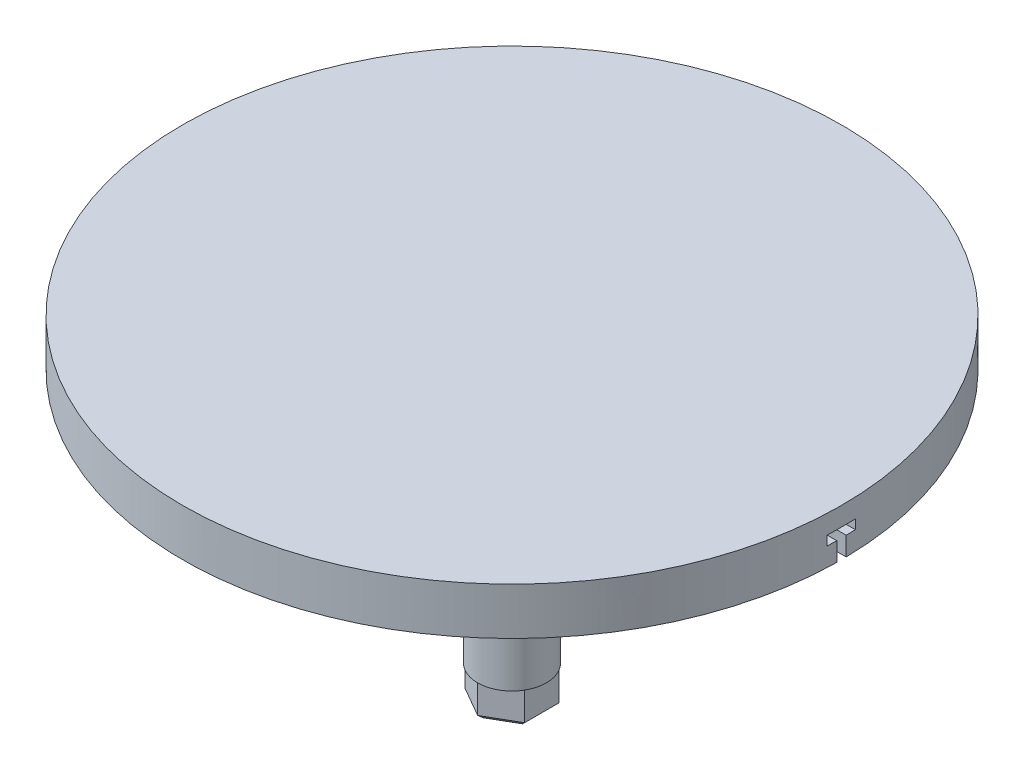
SolidWorks part; units mm, degrees
ref_plane "Front Plane" through (0, 0, 0) normal (0, 0, 1) x (1, 0, 0)
ref_plane "Top Plane" through (0, 0, 0) normal (0, 1, 0) x (1, 0, 0)
ref_plane "Right Plane" through (0, 0, 0) normal (1, 0, 0) x (0, 0, -1)
ref_plane "Plane6" through (0, 3, 0) normal (0, 1, 0) x (1, 0, 0)
sketch "Sketch3" plane through (0, 3, 0) normal (0, 1, 0) x (1, 0, 0)
  circle A0 centre (0, 0) radius 3.65
extrude "Boss-Extrude2" add sketch "Sketch3" along normal blind 27
sketch "Sketch4" plane through (0, 30, 0) normal (0, 1, 0) x (1, 0, 0)
  circle A0 centre (0, 0) radius 35
extrude "Boss-Extrude3" add sketch "Sketch4" along normal blind 5
ref_plane "Plane1" through (35, 0, 0) normal (1, 0, 0) x (0, 0, -1)
sketch "Sketch5" plane through (35, 0, 0) normal (1, 0, 0) x (0, 0, -1)
  line L1 (-0.5, 30) -> (0.5, 30)
  line L2 (0.5, 30) -> (0.5, 32)
  line L3 (-0.5, 32) -> (-1.5, 32)
  line L4 (-1.5, 32) -> (-1.5, 33)
  line L5 (-1.5, 33) -> (1.5, 33)
  line L6 (1.5, 33) -> (1.5, 32)
  line L7 (1.5, 32) -> (0.5, 32)
  line L8 (-0.5, 32) -> (-0.5, 30)
  line L9 (-3.65, 30) -> (3.65, 30) construction
  line L10 (-3.65, 30) -> (3.65, 30) construction
  line L11 (0, 30) -> (0, 28.5625) construction
  dimension "D1" = 2
  dimension "D2" = 2
  dimension "D3" = 1
  dimension "D4" = 3
extrude "Cut-Extrude2" cut sketch "Sketch5" against normal blind 31
ref_plane "Plane2" through (-35, 0, 0) normal (-1, 0, 0) x (0, 0, 1)
sketch "Sketch6" plane through (-35, 0, 0) normal (-1, 0, 0) x (0, 0, 1)
  line L0 (-0.5, 30) -> (-0.5, 32) construction
  line L1 (-0.5, 32) -> (-1.5, 32) construction
  line L2 (-1.5, 33) -> (-1.5, 32) construction
  line L3 (-1.5, 33) -> (1.5, 33) construction
  line L4 (1.5, 32) -> (1.5, 33) construction
  line L5 (1.5, 32) -> (0.5, 32) construction
  line L6 (0.5, 30) -> (0.5, 32) construction
  line L7 (-0.5, 30) -> (-0.5, 32)
  line L8 (-0.5, 32) -> (-1.5, 32)
  line L9 (-1.5, 33) -> (-1.5, 32)
  line L10 (-1.5, 33) -> (1.5, 33)
  line L11 (1.5, 32) -> (1.5, 33)
  line L12 (1.5, 32) -> (0.5, 32)
  line L13 (0.5, 30) -> (0.5, 32)
  line L14 (-0.5, 30) -> (0.5, 30)
  line L16 (-3.65, 30) -> (3.65, 30) construction
  point P10 (0, 30)
  dimension "D1" = 3.65
extrude "Cut-Extrude4" cut sketch "Sketch6" against normal blind 31
ref_plane "Plane3" through (0, 0, -35) normal (0, 0, -1) x (-1, 0, 0)
sketch "Sketch8" plane through (0, 0, -35) normal (0, 0, -1) x (-1, 0, 0)
  line L0 (-0.5, 30) -> (0.5, 30)
  line L1 (0.5, 30) -> (0.5, 32)
  line L2 (-0.5, 32) -> (-1.5, 32)
  line L3 (-1.5, 32) -> (-1.5, 33)
  line L4 (-1.5, 33) -> (1.5, 33)
  line L5 (1.5, 33) -> (1.5, 32)
  line L6 (1.5, 32) -> (0.5, 32)
  line L7 (-0.5, 32) -> (-0.5, 30)
  line L8 (-3.65, 30) -> (-0.5, 30) construction
  dimension "D1" = 2
  dimension "D2" = 2
  dimension "D3" = 1
  dimension "D4" = 3
  dimension "D5" = 3.15
  dimension "D6" = 1
extrude "Cut-Extrude5" cut sketch "Sketch8" against normal blind 31
ref_plane "Plane4" through (24.7487, 0, -24.7487) normal (0.7071, 0, -0.7071) x (0, -1, 0)
sketch "Sketch9" plane through (24.7487, 0, -24.7487) normal (0.7071, 0, -0.7071) x (0, -1, 0)
  line L0 (-30, -0.5) -> (-30, 0.5)
  line L1 (-30, 0.5) -> (-32, 0.5)
  line L2 (-32, -0.5) -> (-32, -1.5)
  line L3 (-32, -1.5) -> (-33, -1.5)
  line L4 (-33, -1.5) -> (-33, 1.5)
  line L5 (-33, 1.5) -> (-32, 1.5)
  line L6 (-32, 1.5) -> (-32, 0.5)
  line L7 (-32, -0.5) -> (-30, -0.5)
  line L8 (-30, -3.65) -> (-30, 3.65) construction
  line L9 (-30, 0) -> (-27.9245, 0) construction
  line L10 (-30, -3.65) -> (-30, 3.65) construction
  dimension "D1" = 2
  dimension "D2" = 2
  dimension "D3" = 1
  dimension "D4" = 3
extrude "Cut-Extrude6" cut sketch "Sketch9" against normal blind 31
ref_plane "Plane5" through (-24.7487, 0, -24.7487) normal (-0.7071, 0, -0.7071) x (0, -1, 0)
sketch "Sketch10" plane through (-24.7487, 0, -24.7487) normal (-0.7071, 0, -0.7071) x (0, -1, 0)
  line L0 (-30, -0.5) -> (-30, 0.5)
  line L1 (-30, 0.5) -> (-32, 0.5)
  line L2 (-32, -0.5) -> (-32, -1.5)
  line L3 (-32, -1.5) -> (-33, -1.5)
  line L4 (-33, -1.5) -> (-33, 1.5)
  line L5 (-33, 1.5) -> (-32, 1.5)
  line L6 (-32, 1.5) -> (-32, 0.5)
  line L7 (-32, -0.5) -> (-30, -0.5)
  line L8 (-30, -3.65) -> (-30, -0.5) construction
  dimension "D1" = 2
  dimension "D2" = 2
  dimension "D3" = 1
  dimension "D4" = 3
  dimension "D5" = 3.15
extrude "Cut-Extrude7" cut sketch "Sketch10" against normal blind 31
sketch "Sketch11" plane through (0, 3, 0) normal (0, -1, 0) x (1, 0, 0)
  line L1 (0, 3.65) -> (-3.161, 1.825)
  line L2 (-3.161, 1.825) -> (-3.161, -1.825)
  line L3 (-3.161, -1.825) -> (0, -3.65)
  line L4 (0, -3.65) -> (3.161, -1.825)
  line L5 (3.161, -1.825) -> (3.161, 1.825)
  line L6 (3.161, 1.825) -> (0, 3.65)
  circle A0 centre (0, 0) radius 3.161 construction
extrude "Boss-Extrude4" add sketch "Sketch11" along normal blind 3.5
fillet "Fillet1" radius 3 1 edges at (0, 30, 3.65)
chamfer "Chamfer1" distance 0.5 angle 45 6 edges at (-1.5805, -0.5, -2.7375) (1.5805, -0.5, -2.7375) (3.161, -0.5, 0) (1.5805, -0.5, 2.7375) (-1.5805, -0.5, 2.7375) (-3.161, -0.5, 0)
